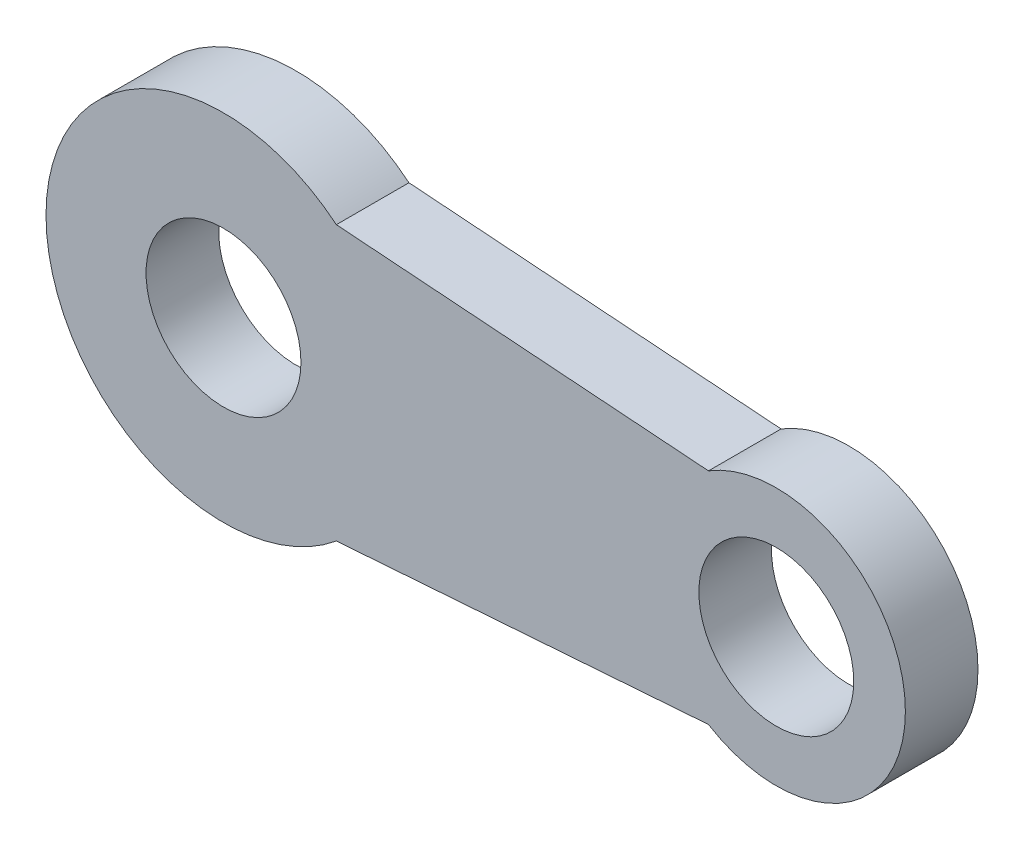
SolidWorks part; units mm, degrees
material "Plain Carbon Steel"
ref_plane "Front Plane" through (0, 0, 0) normal (0, 0, 1) x (1, 0, 0)
ref_plane "Top Plane" through (0, 0, 0) normal (0, 1, 0) x (1, 0, 0)
ref_plane "Right Plane" through (0, 0, 0) normal (1, 0, 0) x (0, 0, -1)
sketch "Sketch1" plane through (0, 0, 0) normal (0, 0, 1) x (1, 0, 0)
  circle A0 centre (0, 0) radius 11
  dimension "D1" = 22
extrude "Boss-Extrude1" add sketch "Sketch1" along normal mid plane 4.5
sketch "Sketch2" plane through (0, 0, 0) normal (0, 0, 1) x (1, 0, 0)
  circle A0 centre (34.26, 0) radius 8
  dimension "D1" = 16
extrude "Boss-Extrude2" add sketch "Sketch2" along normal mid plane 4.5
sketch "Sketch3" plane through (0, 0, 0) normal (0, 0, 1) x (1, 0, 0)
  line L0 (0, -9) -> (34.26, -6.5)
  line L1 (34.26, -6.5) -> (34.26, 6.5)
  line L2 (34.26, 6.5) -> (0, 9)
  line L3 (0, 9) -> (0, -9)
extrude "Boss-Extrude3" add sketch "Sketch3" along normal mid plane 4.5
sketch "Sketch4" plane through (0, 0, 0) normal (0, 0, 1) x (1, 0, 0)
  circle A0 centre (0, 0) radius 4.8
  circle A1 centre (34.26, 0) radius 4.8
  dimension "D1" = 9.6
  dimension "D2" = 9.6
extrude "Cut-Extrude1" cut sketch "Sketch4" against normal mid plane 9
